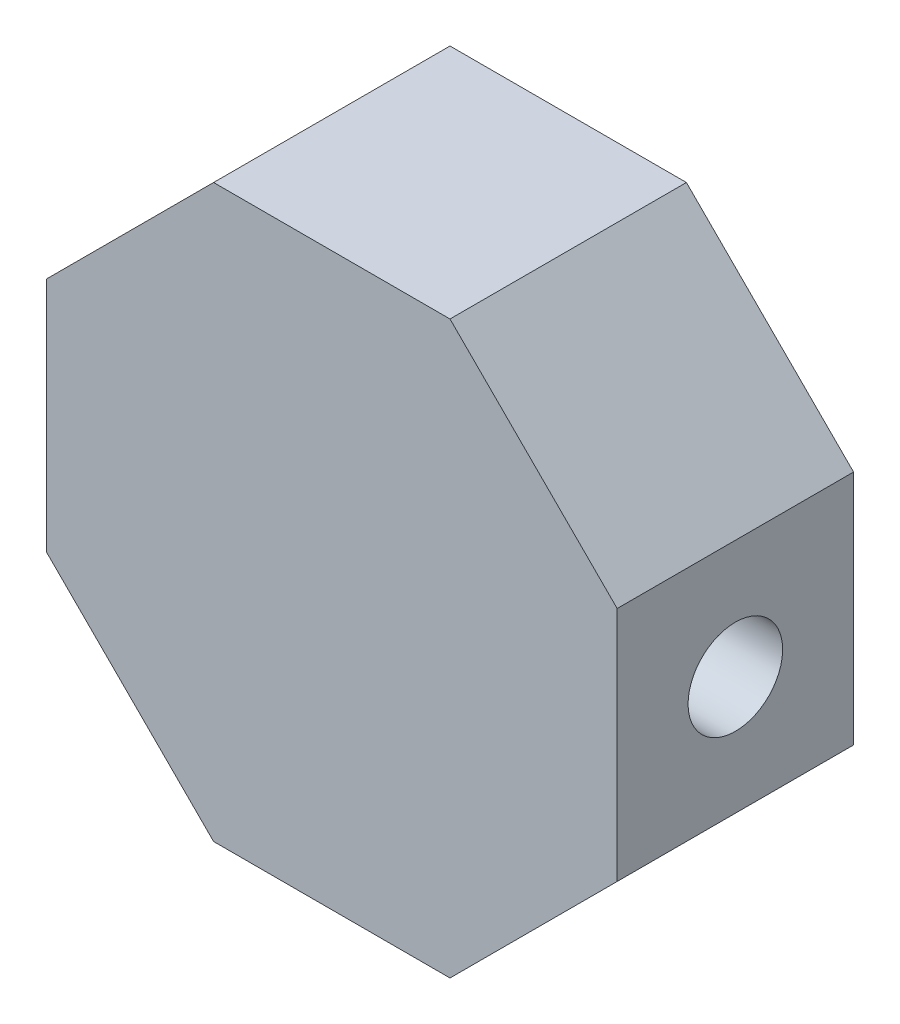
SolidWorks part; units mm, degrees
ref_plane "Front Plane" through (0, 0, 0) normal (0, 0, 1) x (1, 0, 0)
ref_plane "Top Plane" through (0, 0, 0) normal (0, 1, 0) x (1, 0, 0)
ref_plane "Right Plane" through (0, 0, 0) normal (1, 0, 0) x (0, 0, -1)
sketch "Sketch2" plane through (0, 0, 0) normal (0, 0, 1) x (1, 0, 0)
  line L0 (15.3303, 6.35) -> (15.3303, -6.35)
  line L1 (15.3303, -6.35) -> (6.35, -15.3303)
  line L2 (6.35, -15.3303) -> (-6.35, -15.3303)
  line L3 (-6.35, -15.3303) -> (-15.3303, -6.35)
  line L4 (-15.3303, -6.35) -> (-15.3303, 6.35)
  line L5 (-15.3303, 6.35) -> (-6.35, 15.3303)
  line L6 (-6.35, 15.3303) -> (6.35, 15.3303)
  line L7 (6.35, 15.3303) -> (15.3303, 6.35)
extrude "Boss-Extrude1" add sketch "Sketch2" along normal blind 12.7
sketch "Sketch3" plane through (15.3303, 0, 0) normal (1, 0, 0) x (0, 0, -1)
  line L0 (-12.7, 0) -> (0, 0) construction
  line L1 (-12.7, -6.35) -> (-12.7, 6.35) construction
  line L2 (0, -6.35) -> (0, 6.35) construction
  circle A0 centre (-6.35, 0) radius 2.54
  dimension "D1" = 5.08
extrude "Cut-Extrude1" cut sketch "Sketch3" against normal blind 12.7
sketch "Sketch4" plane through (0, 0, 0) normal (0, 0, -1) x (-1, 0, 0)
  circle A0 centre (0, 0) radius 3.175
  dimension "D1" = 6.35
extrude "Cut-Extrude2" cut sketch "Sketch4" against normal blind 2.54
